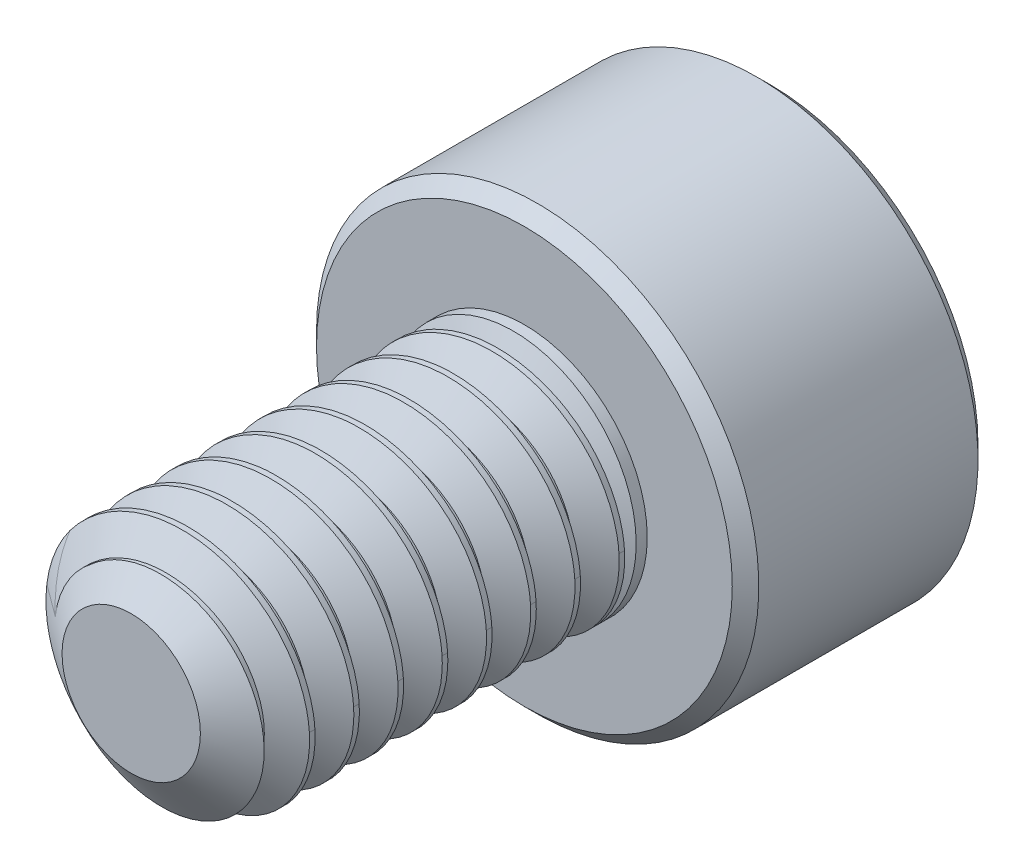
SolidWorks part; units mm, degrees
ref_plane "Front Plane" through (0, 0, 0) normal (0, 0, 1) x (1, 0, 0)
ref_plane "Top Plane" through (0, 0, 0) normal (0, 1, 0) x (1, 0, 0)
ref_plane "Right Plane" through (0, 0, 0) normal (1, 0, 0) x (0, 0, -1)
sketch "Sketch1" plane through (0, 0, 0) normal (0, 0, 1) x (1, 0, 0)
  circle A0 centre (0, 0) radius 1.25
  dimension "OD" = 2.5
extrude "Extrude1" add sketch "Sketch1" against normal blind 4
sketch "Sketch2" plane through (0, 0, 0) normal (0, 0, 1) x (1, 0, 0)
  circle A0 centre (0, 0) radius 1.25 construction
  circle A1 centre (0, 0) radius 1.25
curve "Helix/Spiral1" pitch 0.45 height 4.45 radius 1.25 centre (0, 0, 0) axis (0, 0, -1) start towards (0, 1, 0) parameters "pitch"=0.45
sketch "Sketch3" plane through (0, 0, 0) normal (1, 0, 0) x (0, 0, -1)
  line L0 (-0.3938, 1.25) -> (-0.225, 0.9577)
  line L1 (-0.225, 0.9577) -> (-0.1688, 0.9577)
  line L2 (-0.1688, 0.9577) -> (0, 1.25)
  line L3 (-0.3938, 1.25) -> (0, 1.25)
  line L4 (-0.1969, 1.25) -> (-0.1969, 0.9577) construction
  line L5 (-0.3094, 1.1039) -> (-0.0844, 1.1039) construction
  line L6 (0, 1.25) -> (0, -1.25) construction
  line L7 (0, -1.25) -> (4, -1.25) construction
  point P11 (2.025, -1.25)
  dimension "D1" = 0.0563
  dimension "D2" = 0.225
  dimension "D3" = 60
  dimension "D4" = 2.025
sweep "Cut-Sweep1" cut profiles "Sketch3" path "Helix/Spiral1" align with end faces yes
sketch "Sketch4" plane through (0, 0, 0) normal (1, 0, 0) x (0, 0, -1)
  line L0 (0.3825, 1.25) -> (0, 0.7037)
  line L1 (0, 0.7037) -> (0, 1.25)
  line L2 (0.3825, 1.25) -> (0, 1.25)
  line L3 (-0.3938, 1.25) -> (0, 1.25) construction
  line L4 (0, 0) -> (7.0209, 0) construction
  dimension "D1" = 55
  dimension "D2" = 0.254
revolve "Cut-Revolve1" cut sketch "Sketch4" angle 360 about L4
sketch "Sketch5" plane through (0, 0, 0) normal (1, 0, 0) x (0, 0, -1)
  line L0 (4, -1.0507) -> (4, 0.1042) construction
  line L1 (4, 1.25) -> (0.1203, 1.25)
  line L2 (4, 1.25) -> (4, 0)
  line L3 (4, 0) -> (0.0001, 0)
  line L4 (0.0001, 0.9198) -> (0.0001, 0)
  line L5 (0.1203, 1.25) -> (0.0001, 0.9198)
  line L6 (0, 0) -> (9.9695, 0) construction
  point P3 (0.0001, 1.25)
  point P10 (0.0001, 1.25)
  dimension "D1" = 0.3302
  dimension "Thread min" = 0.0001
  dimension "D3" = 20
revolve "partially thread" [suppressed] add sketch "Sketch5" angle 360 about L6
sketch "Sketch6" plane through (0, 0, -4) normal (0, 0, -1) x (-1, 0, 0)
  circle A0 centre (0, 0) radius 2.25
  dimension "head dia" = 4.5
extrude "Extrude2" add sketch "Sketch6" along normal blind 2.5
sketch "Sketch7" plane through (0, 0, -6.5) normal (0, 0, -1) x (-1, 0, 0)
  line L1 (0, 1.1547) -> (-1, 0.5774)
  line L2 (-1, 0.5774) -> (-1, -0.5774)
  line L3 (-1, -0.5774) -> (0, -1.1547)
  line L4 (0, -1.1547) -> (1, -0.5774)
  line L5 (1, -0.5774) -> (1, 0.5774)
  line L6 (1, 0.5774) -> (0, 1.1547)
  circle A0 centre (0, 0) radius 1 construction
  dimension "hex dia" = 2
extrude "Cut-Extrude1" cut sketch "Sketch7" against normal blind 1.5
sketch "Sketch8" plane through (0, 0, -6.5) normal (0, 0, -1) x (-1, 0, 0)
  circle A0 centre (0, 0) radius 1.1547
extrude "Cut-Extrude2" cut sketch "Sketch8" against normal through all draft 45
chamfer "Chamfer1" distance 0.135 angle 45 2 edges at (-2.25, 0, -6.5) (-2.25, 0, -4)
sketch "Sketch9" plane through (0, 0, 0) normal (1, 0, 0) x (0, 0, -1)
  line L0 (0, 1.25) -> (0, -1.25) construction
  line L1 (2.475, 1.25) -> (2.475, -1.25) construction
  dimension "D1" = 2.475
sketch "Sketch10" plane through (0, 0, 0) normal (1, 0, 0) x (0, 0, -1)
  line L0 (4, 1.25) -> (4, 0)
  line L1 (4, 1.25) -> (3.8875, 1.25)
  line L2 (3.8875, 1.25) -> (3.3697, 0)
  line L3 (4, 0) -> (3.3697, 0)
  line L4 (4, 2.115) -> (4, -2.115) construction
  dimension "D1" = 22.5
  dimension "D2" = 0.1125
revolve "Revolve1" add sketch "Sketch10" angle 360 about L3
equation "\"D3@Helix/Spiral1\" = \"screw length@Extrude1\"+\"pitch@Helix/Spiral1\""
equation "\"D1@Sketch3\" = \"pitch@Helix/Spiral1\"*.125"
equation "\"D2@Sketch3\" = \"pitch@Helix/Spiral1\"*.5"
equation "\"D1@Cut-Extrude1\" = \"hex dia@Sketch7\"*.75"
equation "\"D1@Chamfer1\" = \"head dia@Sketch6\"*.03"
equation "\"D1@Sketch9\" = \"pitch@Helix/Spiral1\"*5.5"
equation "\"D2@Sketch10\" = \"pitch@Helix/Spiral1\"*.25"
equation "\"D4@Sketch3\" = \"pitch@Helix/Spiral1\"*4.50"
